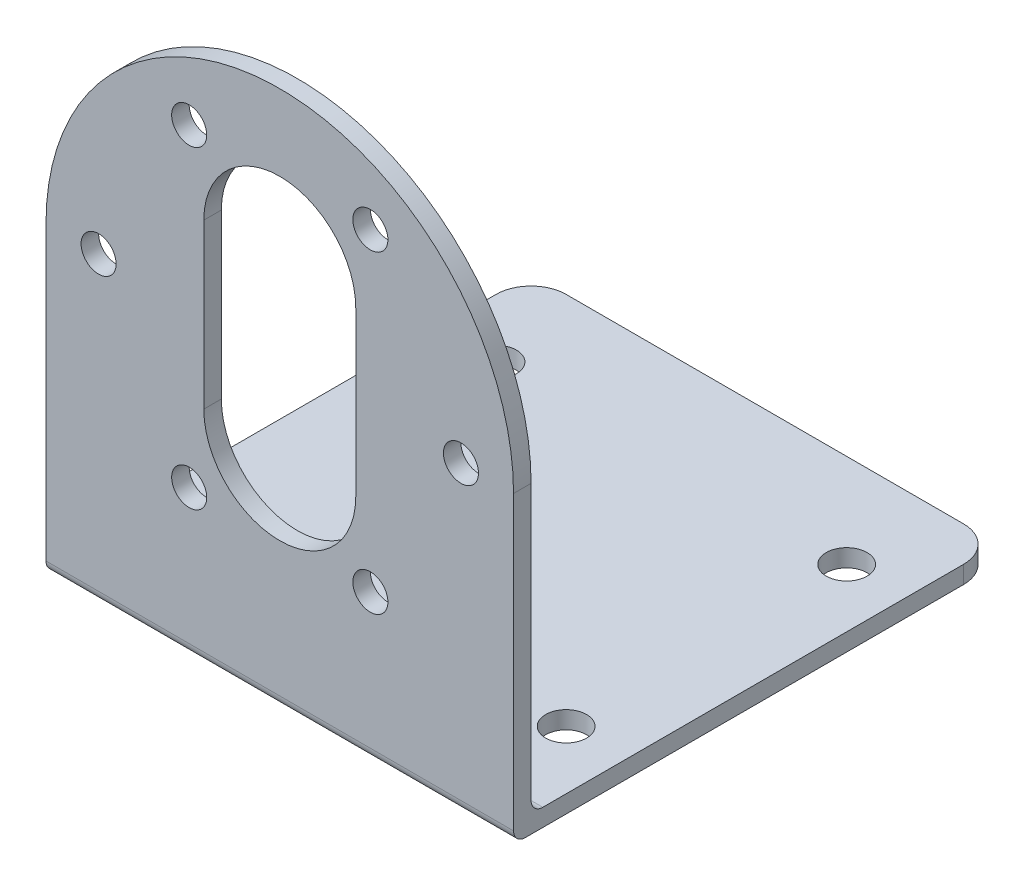
SolidWorks part; units mm, degrees
ref_plane "前视基准面" through (0, 0, 0) normal (0, 0, 1) x (1, 0, 0)
ref_plane "上视基准面" through (0, 0, 0) normal (0, 1, 0) x (1, 0, 0)
ref_plane "右视基准面" through (0, 0, 0) normal (1, 0, 0) x (0, 0, -1)
sketch "草图1" plane through (0, 0, 0) normal (0, 0, 1) x (1, 0, 0)
  line L1 (7.75, -13.4234) -> (15.5, 0) construction
  line L2 (15.5, 0) -> (7.75, 13.4234) construction
  line L3 (7.75, 13.4234) -> (-7.75, 13.4234) construction
  line L4 (-7.75, 13.4234) -> (-15.5, 0) construction
  line L5 (-15.5, 0) -> (-7.75, -13.4234) construction
  line L6 (-7.75, -13.4234) -> (7.75, -13.4234) construction
  line L8 (-20, 0) -> (-20, -26)
  line L9 (-20, -26) -> (20, -26)
  line L10 (20, 0) -> (20, -26)
  line L13 (-6.5, 7) -> (-6.5, -7)
  line L15 (6.5, 7) -> (6.5, -7)
  line L16 (-6.5, 7) -> (6.5, -7) construction
  line L17 (-6.5, -7) -> (6.5, 7) construction
  arc A0 (20, 0) -> (-20, 0) centre (0, 0) ccw
  circle A1 centre (0, 0) radius 15.5 construction
  circle A2 centre (-7.75, 13.4234) radius 1.5
  circle A3 centre (7.75, 13.4234) radius 1.5
  circle A4 centre (15.5, 0) radius 1.5
  circle A5 centre (7.75, -13.4234) radius 1.5
  circle A6 centre (-7.75, -13.4234) radius 1.5
  circle A7 centre (-15.5, 0) radius 1.5
  arc A8 (-6.5, 7) -> (6.5, 7) centre (0, 7) cw
  arc A9 (-6.5, -7) -> (6.5, -7) centre (0, -7) ccw
  point P23 (0.2419, 0.419)
  point P34 (0, 0)
  dimension "D1" = 6
  dimension "D3" = 40
  dimension "D4" = 31
  dimension "D6" = 3
  dimension "D2" = 26
  dimension "D5" = 40
  dimension "D7" = 14
  dimension "D8" = 13
extrude "凸台-拉伸1" add sketch "草图1" along normal blind 1.5 contours A0 L8 L9 L10 A2 region at (0, 19.3904, 0)
sketch "草图2" plane through (0, 0, 0) normal (0, 0, -1) x (-1, 0, 0)
  line L2 (-20, -26) -> (20, -26)
  line L3 (-20, -26) -> (-20, -24.5)
  line L4 (-20, -24.5) -> (20, -24.5)
  line L5 (20, -26) -> (20, -24.5)
  dimension "D1" = 1.5
  dimension "D2" = 40
extrude "凸台-拉伸2" add sketch "草图2" along normal blind 40
sketch "草图3" plane through (0, -24.5, 0) normal (0, 1, 0) x (1, 0, 0)
  line L0 (0, 40) -> (0, 0) construction
  line L1 (-20, 40) -> (20, 40) construction
  line L3 (-15, 32) -> (15, 32) construction
  line L4 (-15, 32) -> (-15, 8) construction
  line L5 (-15, 8) -> (15, 8) construction
  line L6 (15, 32) -> (15, 8) construction
  line L7 (-15, 32) -> (15, 8) construction
  line L8 (-15, 8) -> (15, 32) construction
  circle A0 centre (-15, 32) radius 1.75
  circle A1 centre (-15, 8) radius 1.75
  circle A2 centre (15, 8) radius 1.75
  circle A3 centre (15, 32) radius 1.75
  point P5 (0, 20)
  dimension "D3" = 3.5
  dimension "D4" = 3.5
  dimension "D1" = 30
  dimension "D2" = 24
extrude "切除-拉伸1" cut sketch "草图3" against normal blind 40
fillet "圆角1" radius 3 2 edges at (20, -25.25, -40) (-20, -25.25, -40)
fillet "圆角2" radius 1 2 edges at (0, -26, 1.5) (0, -24.5, 0)
